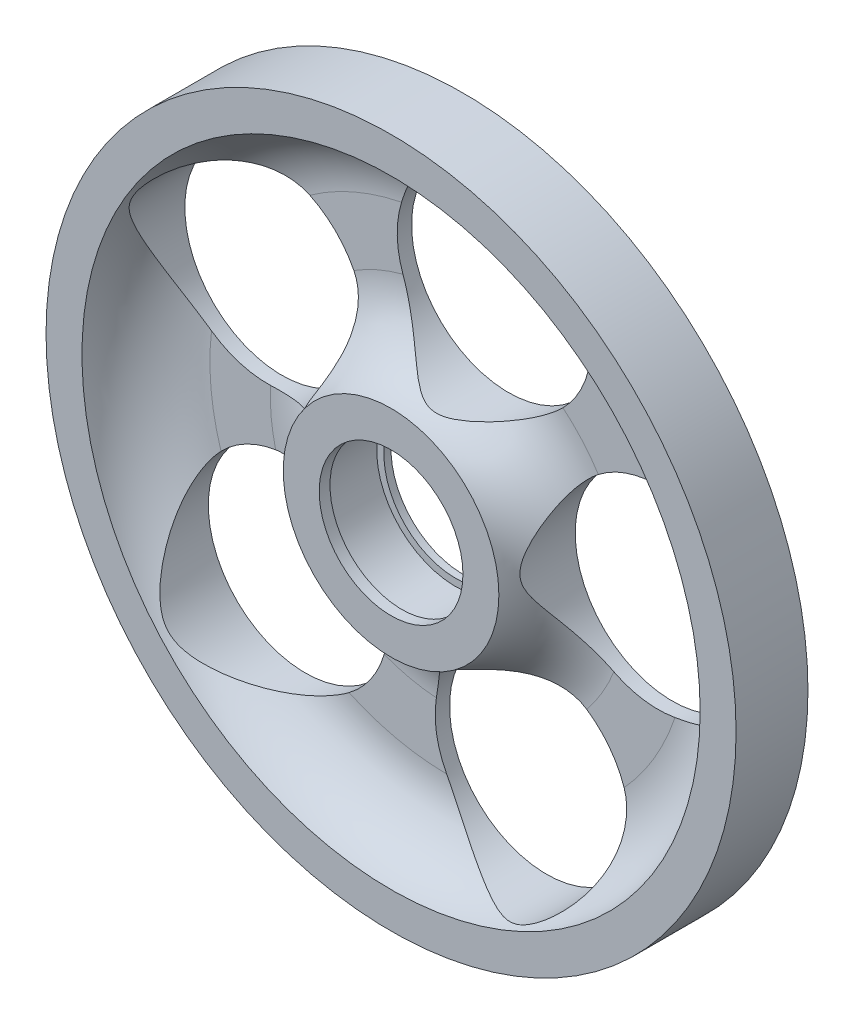
SolidWorks part; units mm, degrees
ref_plane "Front Plane" through (0, 0, 0) normal (0, 0, 1) x (1, 0, 0)
ref_plane "Top Plane" through (0, 0, 0) normal (0, 1, 0) x (1, 0, 0)
ref_plane "Right Plane" through (0, 0, 0) normal (1, 0, 0) x (0, 0, -1)
sketch "Sketch1" plane through (0, 0, 0) normal (0, 0, 1) x (1, 0, 0)
  circle A0 centre (0, 0) radius 10
  circle A1 centre (0, 0) radius 48
  dimension "D1" = 20
  dimension "D2" = 38
extrude "Boss-Extrude1" add sketch "Sketch1" along normal blind 10
sketch "Sketch2" plane through (0, 0, 10) normal (0, 0, 1) x (1, 0, 0)
  circle A0 centre (0, 0) radius 11
  dimension "D1" = 22
extrude "Cut-Extrude1" cut sketch "Sketch2" against normal blind 7.5 from offset 1.5 offset against normal yes
sketch "Sketch3" plane through (0, 0, 10) normal (0, 0, 1) x (1, 0, 0)
  circle A0 centre (0, 0) radius 15
  circle A1 centre (0, 0) radius 43
  circle A2 centre (0, 0) radius 10 construction
  circle A3 centre (0, 0) radius 48 construction
  dimension "D1" = 5
  dimension "D2" = 5
extrude "Cut-Extrude2" cut sketch "Sketch3" against normal blind 8
sketch "Sketch4" plane through (0, 0, 2) normal (0, 0, 1) x (1, 0, 0)
  circle A2 centre (-21.9237, -19.3626) radius 13.5
  circle A4 centre (-25.1898, 14.8673) radius 13.5
  circle A5 centre (6.3556, 28.5512) radius 13.5
  circle A6 centre (29.1178, 2.7782) radius 13.5
  circle A7 centre (11.6402, -26.8341) radius 13.5
  point P14 (0, 0)
  dimension "D1" = 29.25
  dimension "D2" = 27
  dimension "D3" = 5
extrude "Cut-Extrude3" cut sketch "Sketch4" against normal blind 8
fillet "Fillet1" radius 10 2 edges at (43, 0, 2) (15, 0, 2)
